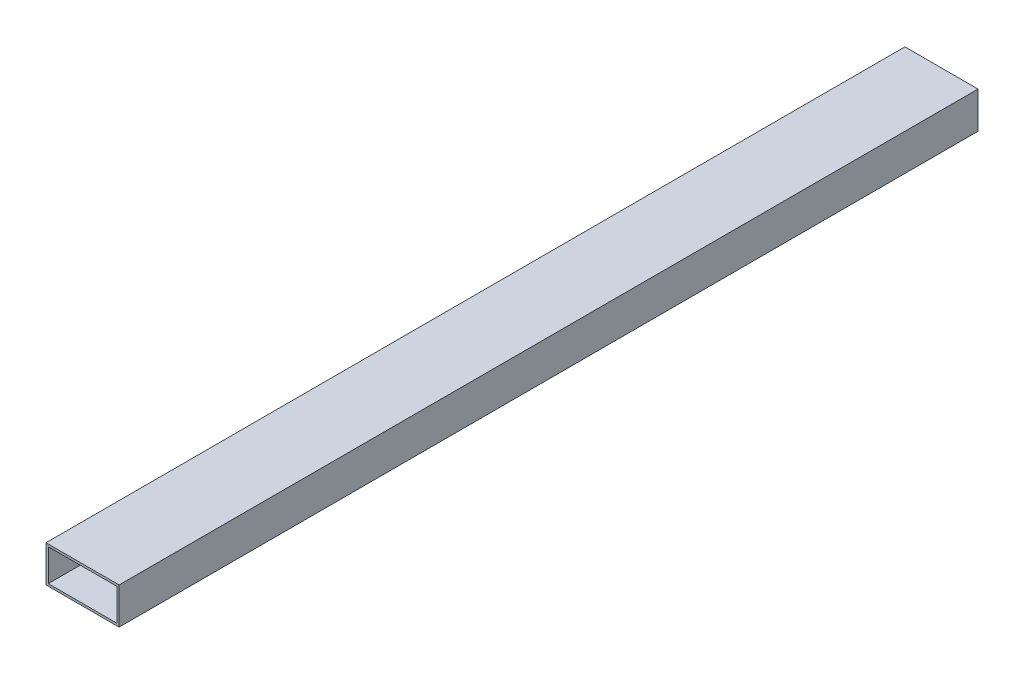
SolidWorks part; units mm, degrees
material "6061-T6 (SS)"
ref_plane "Front Plane" through (0, 0, 0) normal (0, 0, 1) x (1, 0, 0)
ref_plane "Top Plane" through (0, 0, 0) normal (0, 1, 0) x (1, 0, 0)
ref_plane "Right Plane" through (0, 0, 0) normal (1, 0, 0) x (0, 0, -1)
sketch "Sketch1" plane through (0, 0, 0) normal (0, 0, 1) x (1, 0, 0)
  line L1 (0, 0) -> (50.8, 0)
  line L2 (0, 0) -> (0, 25.4)
  line L3 (0, 25.4) -> (50.8, 25.4)
  line L4 (50.8, 0) -> (50.8, 25.4)
  dimension "D1" = 50.8
  dimension "D2" = 25.4
extrude "Boss-Extrude1" add sketch "Sketch1" along normal mid plane 596.9
shell "Shell1" thickness 1.5875 removed face at (25.4, 12.7, -298.45) removed face at (25.4, 12.7, 298.45)
